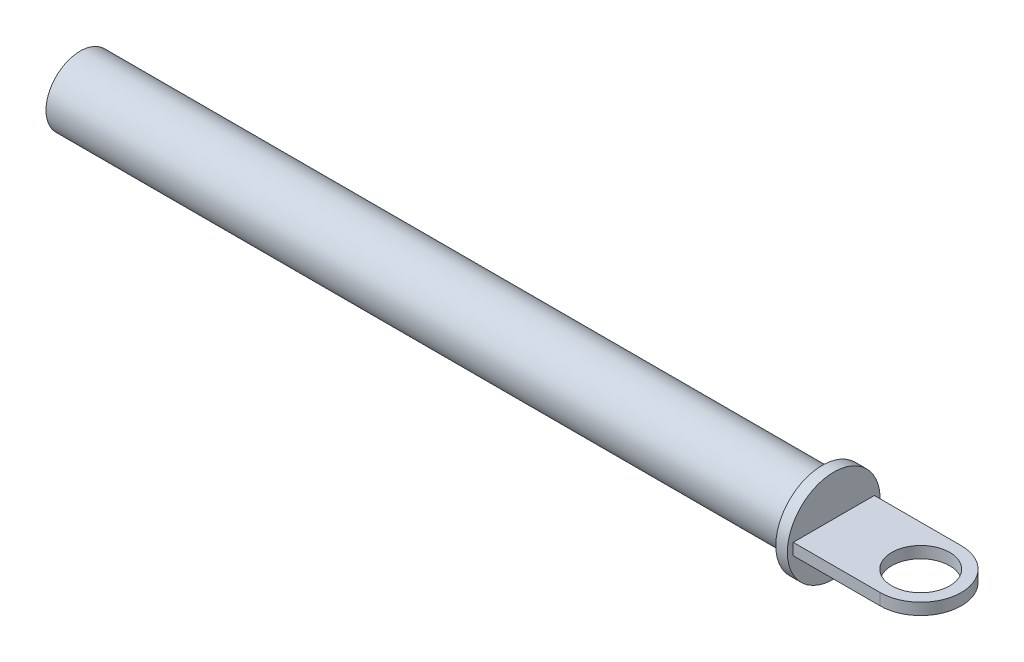
SolidWorks part; units mm, degrees
ref_plane "Front Plane" through (0, 0, 0) normal (0, 0, 1) x (1, 0, 0)
ref_plane "Top Plane" through (0, 0, 0) normal (0, 1, 0) x (1, 0, 0)
ref_plane "Right Plane" through (0, 0, 0) normal (1, 0, 0) x (0, 0, -1)
ref_plane "Plane1" through (0, 0, 0) normal (0, 0, -1) x (-1, 0, 0)
sketch "Sketch1" plane through (0, 0, 0) normal (0, 0, -1) x (-1, 0, 0)
  line L0 (-33, 4) -> (-33, 0)
  line L1 (-33, 0) -> (-32, 0)
  line L2 (-32, 0) -> (-32, 4)
  line L3 (-32, 4) -> (-33, 4)
  line L4 (-33, 0) -> (-32, 0) construction
revolve "Revolve1" add sketch "Sketch1" angle 360 about L4 reverse direction yes
ref_plane "Plane2" through (0, 0.5, 0) normal (0, 1, 0) x (1, 0, 0)
sketch "Sketch2" plane through (0, 0.5, 0) normal (0, 1, 0) x (1, 0, 0)
  line L0 (33, 3.5) -> (33, -3.5)
  line L1 (33, -3.5) -> (40.5, -3.5)
  line L2 (40.5, 3.5) -> (33, 3.5)
  arc A0 (40.5, -3.5) -> (40.5, 3.5) centre (40.5, 0) ccw
extrude "Boss-Extrude1" add sketch "Sketch2" against normal blind 1
sketch "Sketch3" plane through (32, 0, 0) normal (-1, 0, 0) x (0, 0, 1)
  circle A0 centre (0, 0) radius 2.95
  dimension "D1" = 5.9
extrude "Boss-Extrude2" add sketch "Sketch3" along normal blind 64
hole_wizard "Ø5.0 (5) Diameter Hole1" positions "Sketch5" profile "Sketch4" hole size "Ø5.0" standard "ANSI Metric"
sketch "Sketch5" plane through (0, -0.5, 0) normal (0, -1, 0) x (-1, 0, 0)
  point P0 (-40.5, 0)
sketch "Sketch4" plane through (40.5, -0.5, 0) normal (1, 0, 0) x (0, 0, -1)
  line L0 (0, 0) -> (0, 4.5)
  line L1 (0, 4.5) -> (2.5, 4.5)
  line L2 (2.5, 4.5) -> (2.5, 0)
  line L5 (2.5, 0) -> (0, 0)
  line L11 (0, -6.35) -> (0, 107.95) construction
  dimension "Thru Hole Dia." = 5
  dimension "Thru Hole Depth" = 4.5
